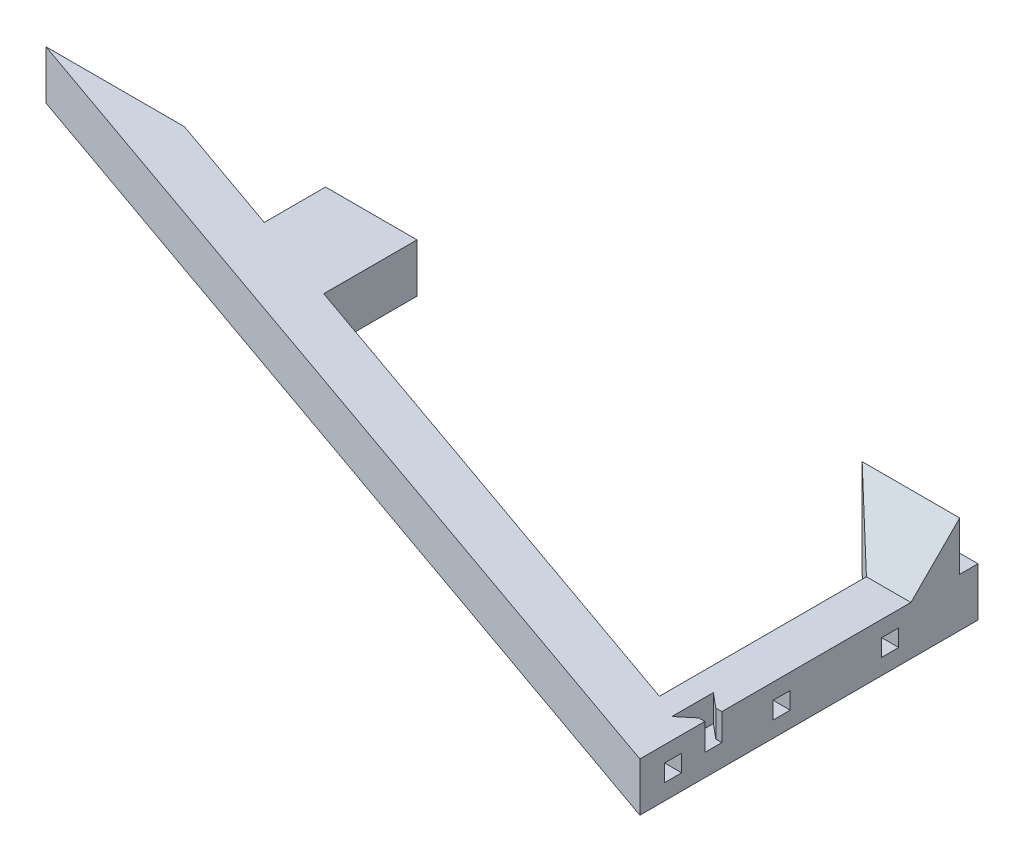
SolidWorks part; units mm, degrees
ref_plane "Přední rovina" through (0, 0, 0) normal (0, 0, 1) x (1, 0, 0)
ref_plane "Horní rovina" through (0, 0, 0) normal (0, 1, 0) x (1, 0, 0)
ref_plane "Pravá rovina" through (0, 0, 0) normal (1, 0, 0) x (0, 0, -1)
sketch "Skica2" plane through (0, 0, 0) normal (0, 1, 0) x (1, 0, 0)
  line L13 (0, 0) -> (0, -55.45)
  line L14 (0, -55.45) -> (-149.85, -3)
  line L15 (-149.85, -3) -> (-127.1478, -3)
  line L16 (-127.1478, -3) -> (-107, -10.0521)
  line L17 (-107, -10.0521) -> (-107, 0)
  line L18 (-107, 0) -> (-92, 0)
  line L19 (-92, 0) -> (-92, -15.3023)
  line L20 (-92, -15.3023) -> (-7.3, -44.9487)
  line L21 (-7.3, -44.9487) -> (-7.3, 0)
  line L22 (-7.3, 0) -> (0, 0)
  dimension "D1" = 55.45
  dimension "D2" = 149.85
  dimension "D3" = 7.5
  dimension "D4" = 15
  dimension "D5" = 7.3
  dimension "D6" = 3
  dimension "D7" = 7.5
  dimension "D8" = 84.7
extrude "Přidat vysunutím1" add sketch "Skica2" along normal blind 8
sketch "Skica3" plane through (0, 8, 0) normal (0, 1, 0) x (1, 0, 0)
  line L6 (0, -42) -> (-1, -42)
  line L7 (0, -55.45) -> (0, 0) construction
  line L8 (-1, -42) -> (-3.4, -40)
  line L9 (-3.4, -40) -> (-3.4, -46.8)
  line L10 (-3.4, -46.8) -> (-1, -44.8)
  line L11 (-1, -44.8) -> (0, -44.8)
  line L12 (0, -44.8) -> (0, -42)
  line L13 (0, 0) -> (-7.3, 0) construction
  dimension "D1" = 1
  dimension "D2" = 1
  dimension "D3" = 6.8
  dimension "D4" = 2.8
  dimension "D5" = 3.4
  dimension "D6" = 2
  dimension "40" = 40
extrude "Odebrat vysunutím1" cut sketch "Skica3" against normal blind 4.4
sketch "Skica5" plane through (0, 8, 0) normal (0, 1, 0) x (1, 0, 0)
  line L10 (0, -42) -> (0, 0) construction
  line L11 (0, -3) -> (-16, -3)
  line L12 (0, -3) -> (0, -11)
  line L13 (0, -11) -> (-16, -11)
  line L14 (-16, -3) -> (-16, -11)
  line L15 (0, 0) -> (-7.3, 0) construction
  dimension "D1" = 3
  dimension "D2" = 8
  dimension "D3" = 16
extrude "Přidat vysunutím2" add sketch "Skica5" against normal blind 16 from offset 8
sketch "Skica6" plane through (0, 0, 0) normal (1, 0, 0) x (0, 0, -1)
  line L3 (-11, 8) -> (-11, 16)
  line L4 (-11, 16) -> (-3, 16)
  line L5 (-3, 16) -> (-11, 8)
extrude "Odebrat vysunutím3" cut sketch "Skica6" against normal through all
sketch "Skica7" plane through (0, 0, 0) normal (0, -1, 0) x (1, 0, 0)
  line L3 (-16, 3) -> (-16, 11)
  line L4 (-16, 11) -> (-7.3, 11)
  line L5 (-7.3, 11) -> (-16, 3)
extrude "Odebrat vysunutím4" cut sketch "Skica7" against normal through all
sketch "Skica4" plane through (0, 0, 0) normal (1, 0, 0) x (0, 0, -1)
  line L0 (-3, 8) -> (0, 8) construction
  line L1 (-51.4, 5.4) -> (-48.6, 5.4)
  line L2 (-51.4, 5.4) -> (-51.4, 2.6)
  line L3 (-51.4, 2.6) -> (-48.6, 2.6)
  line L4 (-48.6, 5.4) -> (-48.6, 2.6)
  line L5 (-33.6, 5.4) -> (-30.8, 5.4)
  line L6 (-33.6, 5.4) -> (-33.6, 2.6)
  line L7 (-33.6, 2.6) -> (-30.8, 2.6)
  line L8 (-30.8, 5.4) -> (-30.8, 2.6)
  line L9 (-15.8, 5.4) -> (-13, 5.4)
  line L10 (-15.8, 5.4) -> (-15.8, 2.6)
  line L11 (-15.8, 2.6) -> (-13, 2.6)
  line L12 (-13, 5.4) -> (-13, 2.6)
  line L13 (-55.45, 8) -> (-44.8, 8) construction
  line L14 (0, 8) -> (0, 0) construction
  dimension "D1" = 2.8
  dimension "D2" = 2.8
  dimension "D3" = 2.8
  dimension "D4" = 2.8
  dimension "D5" = 2.8
  dimension "D6" = 2.8
  dimension "D7" = 2.6
  dimension "D8" = 2.6
  dimension "D9" = 2.6
  dimension "D10" = 13
  dimension "D11" = 15
  dimension "D12" = 15
extrude "Odebrat vysunutím2" cut sketch "Skica4" against normal blind 4.4
